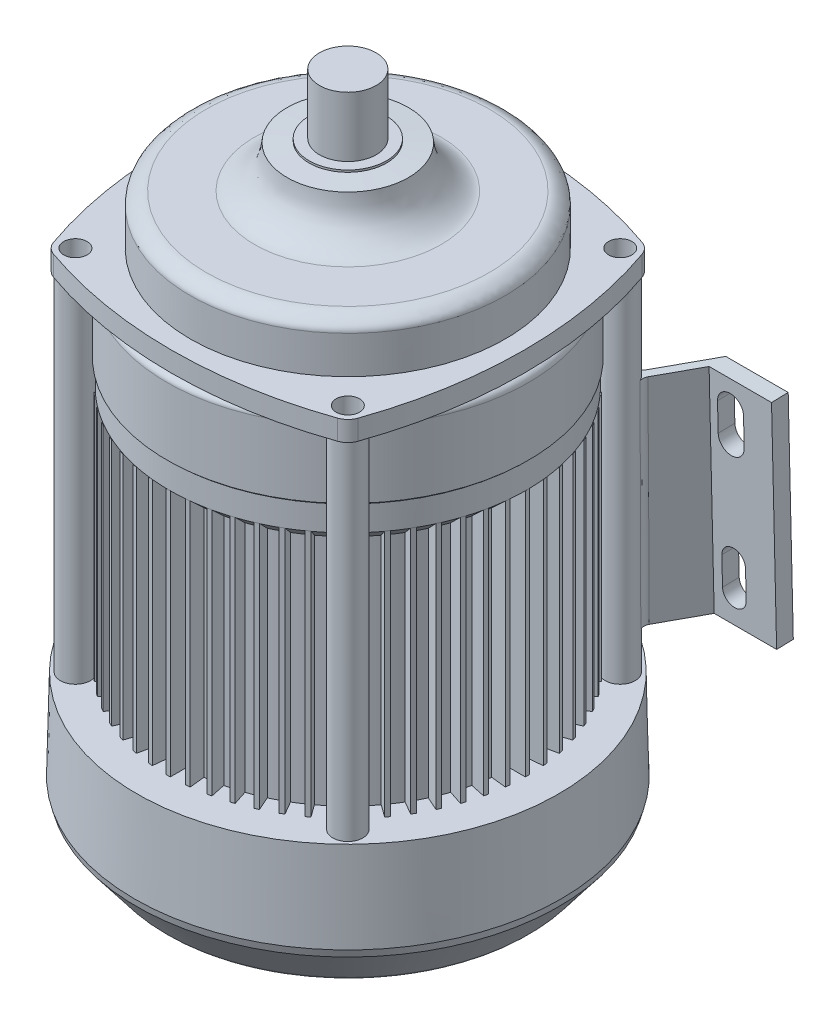
SolidWorks part; units mm, degrees
other "Motor Base"
other "Motor Head"
ref_plane "Front Plane" through (0, 0, 0) normal (0, 0, 1) x (1, 0, 0)
ref_plane "Top Plane" through (0, 0, 0) normal (0, 1, 0) x (1, 0, 0)
ref_plane "Right Plane" through (0, 0, 0) normal (1, 0, 0) x (0, 0, -1)
sketch "Sketch1" plane through (0, 0, 0) normal (0, 0, 1) x (1, 0, 0)
  line L0 (-69.3462, -139.209) -> (170.5518, -139.209) construction
sketch "Sketch3" plane through (0, 0, 0) normal (0, 0, 1) x (1, 0, 0)
  line L0 (-8.5, 0) -> (0, 0) construction
  line L1 (0, 8) -> (0, -197)
  line L2 (-8.5, 0) -> (-8.5, 8)
  line L3 (-8.5, 0) -> (-8.5, -10)
  line L4 (-8.5, -10) -> (-11.6, -10)
  line L5 (-11.6, -10) -> (-11.6, -10.6039)
  line L6 (-27.95, -23.6039) -> (-42.45, -23.6039)
  line L7 (-42.45, -23.6039) -> (-42.45, -27.2539) construction
  line L8 (-42.45, -27.2539) -> (-47.2, -27.2539) construction
  line L9 (-47.2, -27.2539) -> (-47.2, -44.5)
  line L10 (-45.45, -24.7539) -> (-45.45, -27.2539) construction
  line L11 (-11.6, -10.6039) -> (-18.2, -11.0655)
  line L12 (-22.2177, -20.8703) -> (-19.1856, -16.9994) construction
  line L13 (-20.1532, -29.2223) -> (-16.2468, 7.0914) construction
  line L16 (-52.9, -44.5) -> (-47.2, -44.5)
  line L17 (-8.5, 8) -> (0, 8)
  line L18 (0, 8) -> (0, 15.3127) construction
  line L19 (0, -197) -> (-2, -197)
  line L20 (-54.1917, -66.45) -> (-54.1917, -67.05) construction
  line L21 (-54.1917, -46.3) -> (-54.1917, -66.45)
  line L22 (-54.1917, -66.45) -> (-53.5483, -67.05)
  line L23 (-53.5483, -67.05) -> (-53.5483, -74.55)
  line L24 (-47.2, -44.5) -> (0, -44.5)
  line L25 (-52.9, -44.5) -> (0, -44.5) construction
  line L26 (-53.5483, -74.55) -> (-49.2588, -78.55)
  line L27 (-49.2588, -78.55) -> (-49.2588, -148.55)
  line L28 (-49.2588, -148.55) -> (-63.2588, -148.55)
  line L29 (-63.2588, -148.55) -> (-63.8951, -175.55)
  line L30 (-63.8951, -175.55) -> (-63.2588, -177.8444)
  line L31 (-63.2588, -177.8444) -> (-54.4331, -189.3444)
  line L33 (-63.2588, -148.55) -> (-63.2588, -175.55) construction
  arc A1 (-52.9, -44.5) -> (-54.1917, -46.3) centre (-52.2917, -46.3) ccw
  spline S0 degree 3 poles (-18.2, -11.0655) (-18.4832, -13.6984) (-18.7961, -16.5493) (-22.6179, -21.3727) (-26.2709, -23.6039) (-27.95, -23.6039) knots 0 0 0 0 0.435029 0.535029 1 1 1 1
  spline S2 degree 3 poles (-47.2, -27.2539) (-47.2, -26.1869) (-45.306, -24.4455) (-43.5167, -23.6039) (-42.45, -23.6039) knots 0 0 0 0 0.468038 1 1 1 1
  spline S3 degree 3 poles (-54.4331, -189.3444) (-51.4904, -193.1787) (-12.5784, -196.5978) (-6.2, -197) (-2, -197) knots 0 0 0 0 0.440369 1 1 1 1
  dimension "D13" = 6.6
  dimension "D14" = 52.5
  dimension "D21" = 1.9
  dimension "D23" = 1.8
  dimension "D37" = 14.5
  dimension "D38" = 5.5971
  dimension "D18" = 3.2012
  dimension "D19" = 3.2
  dimension "D22" = 12.6
  dimension "D39" = 8.827
  dimension "D2" = 3.65
  dimension "D3" = 4.75
  dimension "D4" = 2.5
  dimension "D5" = 3
  dimension "D6" = 10
  dimension "D7" = 3.1
  dimension "D8" = 0.6039
  dimension "D9" = 14.5
  dimension "D10" = 13
  dimension "D11" = 16.35
  dimension "D12" = 94
  dimension "D15" = 5.7
  dimension "D16" = 2
  dimension "D17" = 8
  dimension "D20" = 8.5
  dimension "D24" = 20.15
  dimension "D25" = 47
  dimension "D26" = 0.6
  dimension "D27" = 7.5
  dimension "D28" = 4
  dimension "D29" = 70
  dimension "D30" = 14
  dimension "D31" = 197
  dimension "D32" = 1.35
  dimension "D33" = 27
  dimension "D34" = 15.5
  dimension "D35" = 142.495
  dimension "D36" = 11.5
  dimension "D40" = 6.14
revolve "Revolve4" add sketch "Sketch3" angle 360 about L18 region at (-18.8402, -27.2585, 0) region at (-27.0884, -121.9509, 0)
sketch "Sketch5" plane through (0, -148.55, 0) normal (0, 1, 0) x (1, 0, 0)
  line L0 (0, 0) -> (0, -63.2588) construction
  line L1 (-0.625, -53.8549) -> (0.625, -53.8549)
  line L6 (-0.625, -53.8549) -> (-0.625, -49.2549)
  line L7 (0.625, -53.8549) -> (0.625, -49.2549)
  circle A0 centre (0, 0) radius 63.2588 construction
  circle A1 centre (0, 0) radius 49.2588 construction
  circle A2 centre (0, 0) radius 49.2588 construction
  arc A3 (-0.625, -49.2549) -> (0.625, -49.2549) centre (0, 0) ccw
  point P0 (0, 0)
  point P10 (0, -53.8549)
  dimension "D1" = 4.6
  dimension "D2" = 1.25
extrude "Boss-Extrude2" add sketch "Sketch5" along normal up to surface (74.2893 mm away) up to face at (0, -78.55, -49.2588)
pattern_circular "CirPattern1" count 60 over 360 about axis through (0, 8, 0) along (0, -1, 0) of "Boss-Extrude2"
ref_plane "Plane1" through (0, -38.5, 0) normal (0, 1, 0) x (1, 0, 0)
sketch "Sketch6" plane through (0, -38.5, 0) normal (0, 1, 0) x (1, 0, 0)
  line L0 (0, 0) -> (57.7588, 0) construction
  line L1 (0, 0) -> (40.8417, 40.8417) construction
  line L3 (-44.8417, -44.8417) -> (44.8417, -44.8417) construction
  line L4 (-44.8417, -44.8417) -> (-44.8417, 44.8417) construction
  line L5 (-44.8417, 44.8417) -> (44.8417, 44.8417) construction
  line L6 (44.8417, -44.8417) -> (44.8417, 44.8417) construction
  line L7 (-44.8417, -44.8417) -> (44.8417, 44.8417) construction
  line L8 (-44.8417, 44.8417) -> (44.8417, -44.8417) construction
  circle A0 centre (0, 0) radius 52.9 construction
  circle A1 centre (0, 0) radius 52.9 construction
  circle A2 centre (0, 0) radius 63.2588 construction
  circle A3 centre (0, 0) radius 63.2588 construction
  circle A4 centre (0, 0) radius 57.7588 construction
  circle A14 centre (-40.8417, 40.8417) radius 4.5
  circle A18 centre (40.8417, 40.8417) radius 3.5
  circle A19 centre (40.8417, -40.8417) radius 3.5
  circle A20 centre (-40.8417, -40.8417) radius 3.5
  circle A21 centre (-40.8417, 40.8417) radius 3.5
  arc A22 (44.8417, 44.8417) -> (44.8417, -44.8417) centre (-75.8927, 0) cw
  arc A23 (-44.8417, 44.8417) -> (44.8417, 44.8417) centre (0, -75.8927) cw
  arc A24 (-44.8417, 44.8417) -> (-44.8417, -44.8417) centre (75.8927, 0) ccw
  arc A25 (-44.8417, -44.8417) -> (44.8417, -44.8417) centre (0, 75.8927) ccw
  circle A26 centre (40.8417, 40.8417) radius 4.5
  circle A27 centre (40.8417, -40.8417) radius 4.5
  circle A28 centre (-40.8417, -40.8417) radius 4.5
  point P6 (0, 0)
  point P12 (52.9, 0)
  point P20 (0, 0)
  point P27 (0, -52.9)
  dimension "D3" = 7
  dimension "D1" = 5.5
  dimension "D2" = 45
  dimension "D5" = 4
  dimension "D6" = 4
  dimension "D7" = 1
  dimension "D8" = 1
  dimension "D4" = 4
extrude "Boss-Extrude5" add sketch "Sketch6" against normal up to surface (6 mm away) contours A24 A25 A22 A23 A28 A27 A26 A14 | A28 A20 | A27 A19 | A26 A18 | A14 A21 region at (-45.2144, -38.5, -40.8417) region at (0, -38.5, 0) region at (36.4689, -38.5, -40.8417) region at (36.4689, -38.5, 40.8417) region at (-45.2144, -38.5, 40.8417)
extrude "Boss-Extrude6" add sketch "Sketch6<4>" against normal up to surface (110.05 mm away) contours A26 A18 | A14 A21 | A27 A19 | A28 A20 region at (-45.2144, -38.5, -40.8417) region at (36.4689, -38.5, -40.8417) region at (36.4689, -38.5, 40.8417) region at (-45.2144, -38.5, 40.8417) up to face at (0, -148.55, -63.2588)
sketch "Sketch6<4>" plane through (0, -38.5, 0) normal (0, 1, 0) x (1, 0, 0) same geometry as "Sketch6"
fillet "Fillet2" radius 5 4 edges at (44.8417, -41.5, 44.8417) (44.8417, -41.5, -44.8417) (-44.8417, -41.5, 44.8417) (-44.8417, -41.5, -44.8417)
ref_plane "Plane2" through (0, 1.4075, -59.7249) normal (0, 0.0236, -0.9997) x (-1, 0, 0)
sketch "Sketch7" plane through (0, 1.4075, -59.7249) normal (0, 0.0236, -0.9997) x (-1, 0, 0)
  line L0 (-58, -137.7) -> (-70.6, -137.7)
  line L1 (-70.6, -137.7) -> (-70.6, -72.8)
  line L2 (-70.6, -72.8) -> (-53.75, -72.8)
  line L3 (0, 0) -> (0, -214.7784) construction
  line L4 (-58.1192, -133.2) -> (-58.1192, -117.2) construction
  line L5 (-58.1192, -120.925) -> (-58.1192, -129.475) construction
  line L6 (-54.5692, -120.925) -> (-54.5692, -129.475)
  line L7 (-61.6692, -120.925) -> (-61.6692, -129.475)
  line L8 (-58.1192, -76.9) -> (-58.1192, -92.9) construction
  line L9 (-58.1192, -89.175) -> (-58.1192, -80.625) construction
  line L10 (-62.0192, -89.175) -> (-62.0192, -80.625)
  line L11 (-54.2192, -89.175) -> (-54.2192, -80.625)
  line L12 (-51.8792, -72.8) -> (-51.8792, -137.7)
  line L13 (-53.75, -72.8) -> (-51.8792, -72.8)
  line L14 (-58, -137.7) -> (-51.8792, -137.7)
  arc A0 (-54.5692, -120.925) -> (-61.6692, -120.925) centre (-58.1192, -120.925) ccw
  arc A1 (-61.6692, -129.475) -> (-54.5692, -129.475) centre (-58.1192, -129.475) ccw
  arc A2 (-62.0192, -89.175) -> (-54.2192, -89.175) centre (-58.1192, -89.175) ccw
  arc A3 (-54.2192, -80.625) -> (-62.0192, -80.625) centre (-58.1192, -80.625) ccw
  point P10 (-58.1192, -125.2)
  point P19 (-58.1192, -84.9)
  dimension "D10" = 3.55
  dimension "D13" = 3.9
  dimension "D1" = 58
  dimension "D2" = 137.7
  dimension "D3" = 12.6
  dimension "D4" = 72.8
  dimension "D5" = 53.75
  dimension "D6" = 16
  dimension "D7" = 4.5
  dimension "D8" = 58.1192
  dimension "D9" = 8.55
  dimension "D11" = 76.9
  dimension "D12" = 8.55
  dimension "D14" = 6.24
extrude "Boss-Extrude7" add sketch "Sketch7" against normal blind 5 separate body
sketch "Sketch9" plane through (0, -137.6618, -3.2442) normal (0, -0.9997, -0.0236) x (1, 0, 0)
  line L0 (51.8792, -54.7415) -> (43.2173, -39.9001)
  line L1 (51.8792, -59.7415) -> (40.8417, -40.8295)
  line L2 (51.8792, -59.7415) -> (51.8792, -54.7415)
  line L3 (40.8417, -40.8295) -> (43.2173, -39.9001)
  ellipse E0 centre (40.8417, -37.3305) end of major axis (44.3417, -37.3305) minor radius 3.499 construction
  ellipse E1 centre (40.8417, -37.3305) end of major axis (44.3417, -37.3305) minor radius 3.499 construction
  point P13 (40.8417, -37.3305)
extrude "Boss-Extrude8" add sketch "Sketch9" against normal up to surface (64.9 mm away) up to face at (61.2396, -71.4312, -58.9407)
mirror "Mirror2" about plane through (0, 0, 0) normal (1, 0, 0) of "Boss-Extrude8", "Boss-Extrude7"
extrude "Cut-Extrude1" cut sketch "Sketch6<5>" against normal up to surface (110.05 mm away) contours A18 | A21 region at (40.8417, -38.5, -40.8417) region at (-40.8417, -38.5, -40.8417) up to face at (-40.8417, -148.55, 36.3417)
sketch "Sketch6<5>" plane through (0, -38.5, 0) normal (0, 1, 0) x (1, 0, 0) same geometry as "Sketch6"
fillet "Fillet3" radius 2.5 4 edges at (-41.9484, -104.6306, -45.2034) (-44.1271, -103.8104, -43.9167) (41.9484, -104.6306, -45.2034) (44.1271, -103.8104, -43.9167)
ref_plane "Plane3" through (0, -148.55, 0) normal (0, 1, 0) x (1, 0, 0)
split "Split1" trim tools "Plane3" bodies to split 112 resulting bodies 113 114
ref_plane "Plane4" through (0, 0, -15) normal (0, 0, 1) x (1, 0, 0)
sketch "Sketch11" plane through (0, 0, -15) normal (0, 0, 1) x (1, 0, 0)
  line L0 (-58.8, -120.9) -> (-58.8, -138.4) construction
  point P2 (0, 0)
  dimension "D1" = 58.8
  dimension "D2" = 120.9
  dimension "D3" = 17.5
sketch "Sketch12" plane through (0, 0, 0) normal (1, 0, 0) x (0, 0, -1)
  line L0 (15, -120.9) -> (15, -138.4) construction
  line L4 (15, -134.65) -> (15, -124.65) construction
  line L5 (11.25, -134.65) -> (11.25, -124.65)
  line L6 (18.75, -134.65) -> (18.75, -124.65)
  arc A2 (11.25, -134.65) -> (18.75, -134.65) centre (15, -134.65) ccw
  arc A3 (18.75, -124.65) -> (11.25, -124.65) centre (15, -124.65) ccw
  point P0 (15, -120.9)
  point P5 (15, -129.65)
  point P10 (15, -120.9)
  point P11 (15, -134.5246)
  dimension "D1" = 7.5
extrude "Boss-Extrude9" add sketch "Sketch12" against normal blind 62
fillet "Fillet4" radius 1 4 edges at (-62, -129.65, -18.75) (-62, -138.4, -15) (-62, -129.65, -11.25) (-62, -120.9, -15)
